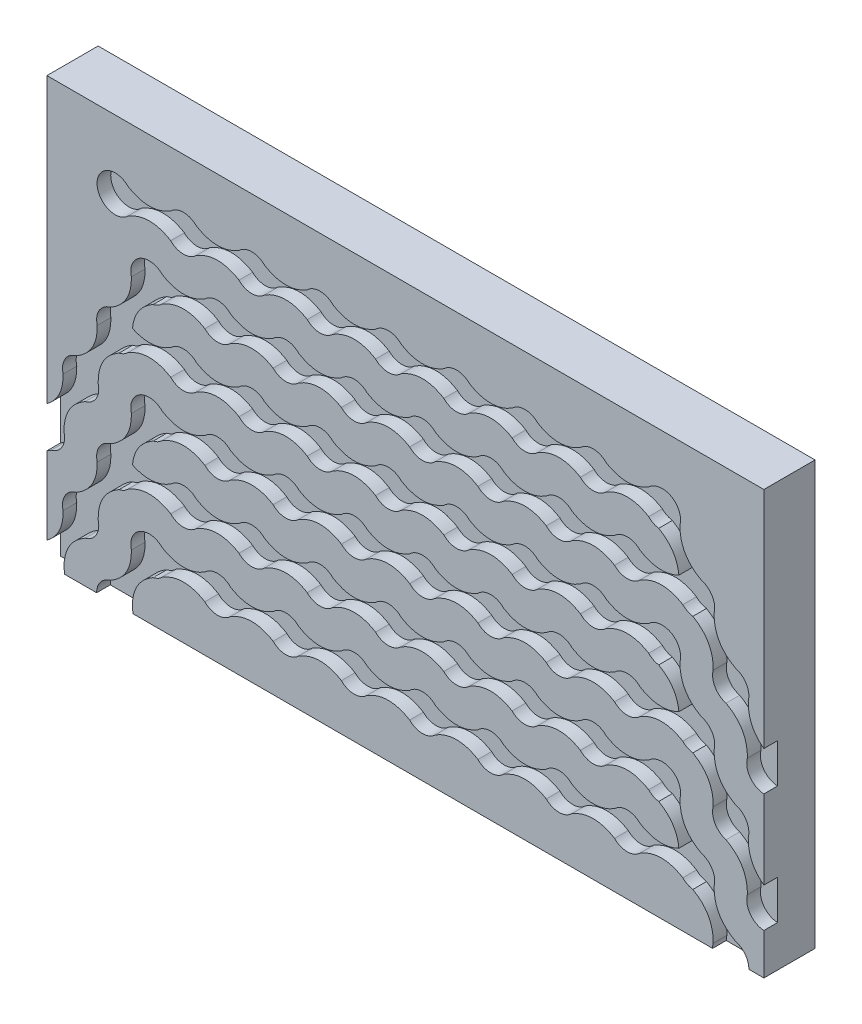
SolidWorks part; units mm, degrees
ref_plane "Front Plane" through (0, 0, 0) normal (0, 0, 1) x (1, 0, 0)
ref_plane "Top Plane" through (0, 0, 0) normal (0, 1, 0) x (1, 0, 0)
ref_plane "Right Plane" through (0, 0, 0) normal (1, 0, 0) x (0, 0, -1)
sketch "Sketch2" plane through (0, 0, 0) normal (0, 0, 1) x (1, 0, 0)
  line L1 (-31.0609, 47.3202) -> (102.2891, 47.3202)
  line L2 (-31.0609, 47.3202) -> (-31.0609, -31.371)
  line L3 (-31.0609, -31.371) -> (102.2891, -31.371)
  line L4 (102.2891, 47.3202) -> (102.2891, -31.371)
  dimension "D1" = 133.35
  dimension "D2" = 78.6911
extrude "Boss-Extrude1" add sketch "Sketch2" along normal blind 9.525
sketch "Sketch1" plane through (0, 0, 9.525) normal (0, 0, 1) x (1, 0, 0)
  line L0 (-23.8319, 34.6202) -> (-5.6609, 34.6202) construction
  line L1 (-18.3609, 34.6202) -> (-18.3609, 37.9936) construction
  line L2 (-12.0109, 28.2702) -> (-12.0109, 40.9702) construction
  line L3 (-18.3609, 34.6202) -> (-12.0109, 40.9702) construction
  line L4 (-12.0109, 40.9702) -> (-5.6609, 34.6202) construction
  line L5 (-18.3609, 35.8108) -> (-12.0109, 35.8108) construction
  line L6 (102.2891, 47.3202) -> (-31.0609, 47.3202) construction
  line L9 (-31.0609, 47.3202) -> (-31.0609, -31.371) construction
  arc A0 (-15.9755, 37.0056) -> (-15.9755, 32.2348) centre (-18.3609, 34.6202) ccw
  arc A1 (-8.0463, 32.2348) -> (-8.0463, 37.0056) centre (-5.6609, 34.6202) ccw
  spline S0 degree 2 poles (-15.9755, 37.0056) (-12.0109, 34.616) (-8.0463, 37.0056) knots 0 0 0 1 1 1
  spline S1 degree 2 poles (-15.9755, 32.2348) (-12.0109, 34.6243) (-8.0463, 32.2348) knots 0 0 0 1 1 1
  point P6 (-15.9755, 37.0056)
  point P7 (-12.0109, 34.6202)
  point P10 (-8.0463, 37.0056)
  dimension "D1" = 6.7469
  dimension "D2" = 6.7469
  dimension "D3" = 12.7
  dimension "D4" = 1.1906
  dimension "D5" = 12.7
  dimension "D6" = 12.7
extrude "Cut-Extrude1" cut sketch "Sketch1" against normal blind 2.54
pattern_linear "LPattern1" count 8 spacing 12.7 along (1, 0, 0) of "Cut-Extrude1"
sketch "Sketch3" plane through (0, 0, 6.985) normal (0, 0, 1) x (1, 0, 0)
  line L0 (113.141, 113.41) -> (138.864, 68.8563) construction
pattern_linear "LPattern3" count 2 spacing 12.7 along (0.5, -0.866, 0) of "LPattern1"
pattern_linear "LPattern4" count 3 spacing 21.997 along (0, -1, 0) of "LPattern3", "LPattern1", "Cut-Extrude1"
sketch "Sketch6" plane through (0, 0, 9.525) normal (0, 0, 1) x (1, 0, 0)
  line L0 (81.7399, 37.5659) -> (89.7766, 23.6459) construction
  line L1 (83.4266, 34.6444) -> (86.3481, 36.3312) construction
  line L2 (81.1024, 25.9702) -> (92.1009, 32.3202) construction
  line L3 (83.4266, 34.6444) -> (92.1009, 32.3202) construction
  line L4 (92.1009, 32.3202) -> (89.7766, 23.6459) construction
  line L5 (84.4577, 35.2398) -> (87.6327, 29.7405) construction
  arc A0 (86.6851, 33.7713) -> (82.5535, 31.386) centre (83.4266, 34.6444) ccw
  arc A1 (86.5181, 24.519) -> (90.6497, 26.9044) centre (89.7766, 23.6459) ccw
  spline S0 degree 2 poles (86.6851, 33.7713) (86.5981, 29.1431) (90.6497, 26.9044) knots 0 0 0 1 1 1
  spline S1 degree 2 poles (82.5535, 31.386) (86.6052, 29.1472) (86.5181, 24.519) knots 0 0 0 1 1 1
  point P5 (86.6851, 33.7713)
  point P6 (86.6016, 29.1452)
  point P9 (90.6497, 26.9044)
  dimension "D1" = 6.7469
  dimension "D2" = 6.7469
  dimension "D3" = 12.7
  dimension "D4" = 1.1906
extrude "Cut-Extrude2" cut sketch "Sketch6" against normal blind 2.54
pattern_linear "LPattern5" count 3 spacing 12.7 along (0.5, -0.866, 0) of "Cut-Extrude2"
pattern_linear "LPattern6" count 3 spacing 21.997 along (0, -1, 0) of "LPattern5"
sketch "Sketch7" plane through (0, 0, 9.525) normal (0, 0, 1) x (1, 0, 0)
  line L0 (-21.1778, 7.8871) -> (-12.0923, 23.6237) construction
  line L1 (-18.4423, 12.6252) -> (-21.3638, 14.3119) construction
  line L2 (-9.768, 14.9494) -> (-20.7665, 21.2994) construction
  line L3 (-18.4423, 12.6252) -> (-20.7665, 21.2994) construction
  line L4 (-20.7665, 21.2994) -> (-12.0923, 23.6237) construction
  line L5 (-19.4734, 13.2205) -> (-16.2984, 18.7197) construction
  arc A0 (-19.3154, 15.8837) -> (-15.1838, 13.4983) centre (-18.4423, 12.6252) ccw
  arc A1 (-11.2192, 20.3652) -> (-15.3508, 22.7506) centre (-12.0923, 23.6237) ccw
  spline S0 degree 2 poles (-19.3154, 15.8837) (-15.2637, 18.1224) (-15.3508, 22.7506) knots 0 0 0 1 1 1
  spline S1 degree 2 poles (-15.1838, 13.4983) (-15.2709, 18.1265) (-11.2192, 20.3652) knots 0 0 0 1 1 1
  point P5 (-19.3154, 15.8837)
  point P6 (-15.2673, 18.1244)
  point P9 (-15.3508, 22.7506)
  dimension "D1" = 6.7469
  dimension "D2" = 6.7469
  dimension "D3" = 12.7
  dimension "D4" = 1.1906
extrude "Cut-Extrude3" cut sketch "Sketch7" against normal blind 2.54
sketch "Sketch8" plane through (0, 0, 9.525) normal (0, 0, 1) x (1, 0, 0)
  line L0 (-130.9367, -65.4959) -> (-114.4625, -36.9619) construction
pattern_linear "LPattern7" count 4 spacing 12.7 along (-0.5, -0.866, 0) of "Cut-Extrude3"
pattern_linear "LPattern8" count 3 spacing 21.997 along (0, -1, 0) of "LPattern7"
scale "Scale1" scale about centroid uniform scaling yes scale factor 0.75
equation "\"large_diameter\" = 1/4in"
equation "\"small_diameter\" = 1/8in"
equation "\"arc_height\" = 1/32in"
equation "\"chain_space\" = 1/2in"
equation "\"chain_thickness\" = 1/32in"
equation "\"outer_height\" = 3/16in"
equation "\"inner_height\" = 2/16in"
equation "\"give\" = 1/64in"
equation "\"board_base\" = 10"
equation "\"board_rows\" = 3"
equation "\"D2@Sketch1\"= \"large_diameter\" + \"give\""
equation "\"D3@Sketch1\"= \"chain_space\""
equation "\"D4@Sketch1\"= \"arc_height\" + \"give\""
equation "\"D1@Sketch2\"=\"chain_space\"*(\"board_base\"+.5)"
equation "\"D3@LPattern1\"=\"chain_space\""
equation "\"D1@LPattern1\"=\"board_base\"-2"
equation "\"D3@LPattern3\"=\"chain_space\""
equation "\"D3@LPattern4\"=\"chain_space\"*sin(60)*2"
equation "\"D2@Sketch2\"=\"board_rows\"*\"chain_space\"*2*sin(60)+.5"
equation "\"D3@LPattern6\"=\"chain_space\"*sin(60)*2"
equation "\"D3@LPattern7\"=\"chain_space\""
equation "\"D3@LPattern8\"=\"chain_space\"*2*sin(60)"
